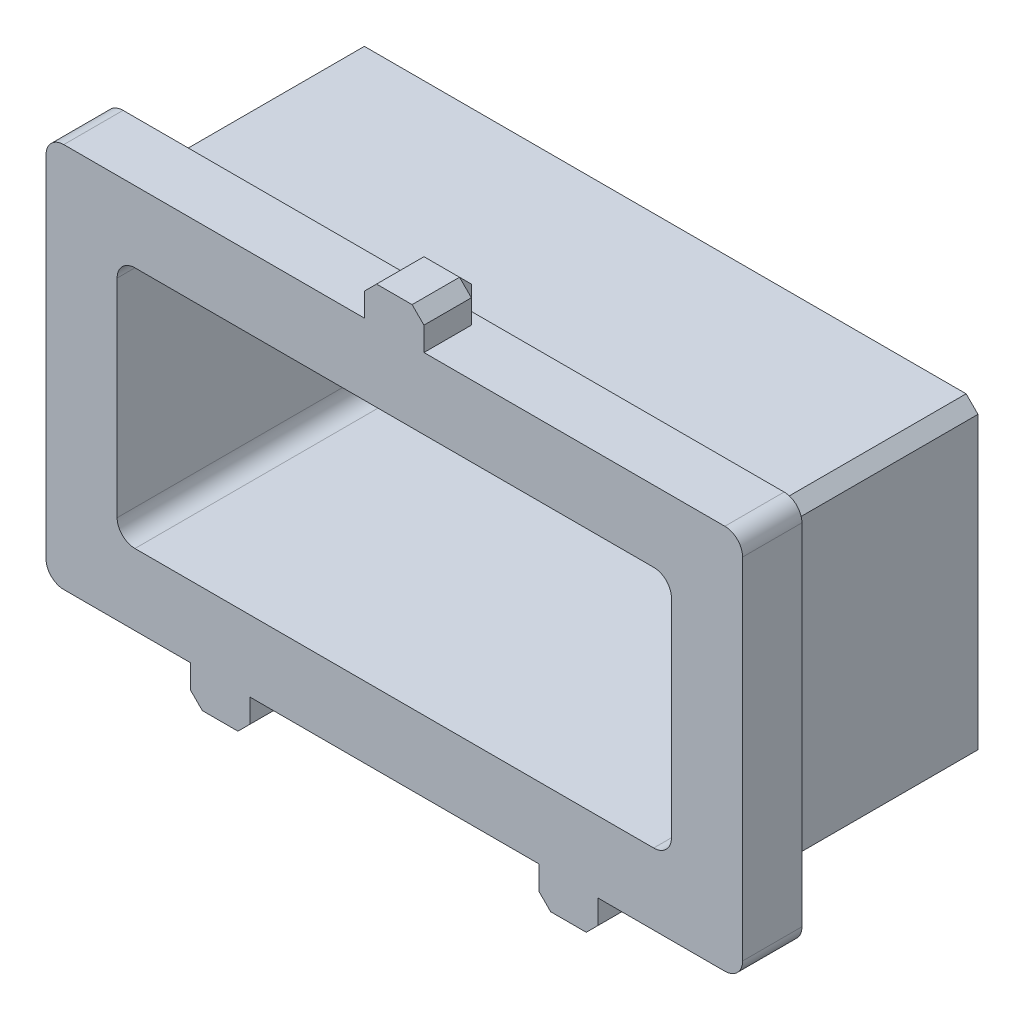
SolidWorks part; units mm, degrees
ref_plane "Front Plane" through (0, 0, 0) normal (0, 0, 1) x (1, 0, 0)
ref_plane "Top Plane" through (0, 0, 0) normal (0, 1, 0) x (1, 0, 0)
ref_plane "Right Plane" through (0, 0, 0) normal (1, 0, 0) x (0, 0, -1)
sketch "Sketch1" plane through (0, 0, 0) normal (0, 0, 1) x (1, 0, 0)
  line L4 (29.8204, 195.8186) -> (29.8204, 202.5496)
  line L5 (29.8204, 202.5496) -> (16.4219, 202.5496)
  line L6 (16.4219, 202.5496) -> (16.4219, 195.8186)
  line L7 (16.4219, 195.8186) -> (29.8204, 195.8186)
  line L8 (29.8204, 195.8186) -> (29.8204, 202.5496)
  line L9 (29.8204, 202.5496) -> (16.4219, 202.5496)
  line L10 (16.4219, 202.5496) -> (16.4219, 195.8186)
  line L11 (16.4219, 195.8186) -> (29.8204, 195.8186)
  dimension "D1" = 0
extrude "Extrude-Thin1" add sketch "Sketch1" along normal blind 5.8039 thin thin type one direction reverse wall 0.762
sketch "Sketch2" plane through (0, 0, 5.8039) normal (0, 0, 1) x (1, 0, 0)
  line L4 (16.4219, 195.8186) -> (29.8204, 195.8186)
  line L5 (29.8204, 195.8186) -> (29.8204, 202.5496)
  line L6 (29.8204, 202.5496) -> (16.4219, 202.5496)
  line L7 (16.4219, 202.5496) -> (16.4219, 195.8186)
  line L8 (16.4219, 195.8186) -> (29.8204, 195.8186)
  line L9 (29.8204, 195.8186) -> (29.8204, 202.5496)
  line L10 (29.8204, 202.5496) -> (16.4219, 202.5496)
  line L11 (16.4219, 202.5496) -> (16.4219, 195.8186)
  dimension "D1" = 0
extrude "Extrude-Thin2" add sketch "Sketch2" against normal blind 1.27 thin thin type one direction wall 0.762
sketch "Sketch4" plane through (0, 0, 5.8039) normal (0, 0, 1) x (1, 0, 0)
  line L0 (15.6599, 203.3116) -> (23.1211, 203.3116) construction
  line L1 (30.5824, 203.3116) -> (15.6599, 203.3116) construction
  line L2 (23.1211, 203.3116) -> (30.5824, 203.3116) construction
  line L3 (23.1211, 203.3116) -> (23.1211, 204.0736) construction
  line L4 (23.1211, 203.3116) -> (23.1211, 204.0736) construction
  line L5 (15.6599, 195.0566) -> (30.5824, 195.0566) construction
  line L6 (23.7561, 203.3116) -> (23.7561, 204.0736)
  line L7 (15.6599, 195.0566) -> (19.3905, 195.0566) construction
  line L8 (22.4861, 203.3116) -> (22.4861, 204.0736)
  line L9 (19.3905, 195.0566) -> (23.1211, 195.0566) construction
  line L10 (23.1211, 195.0566) -> (26.8517, 195.0566) construction
  line L11 (23.7561, 203.3116) -> (22.4861, 203.3116)
  line L12 (23.7561, 204.0736) -> (22.4861, 204.0736)
  line L13 (26.8517, 195.0566) -> (30.5824, 195.0566) construction
  line L14 (30.5824, 195.0566) -> (30.5824, 203.3116) construction
  line L16 (27.4867, 195.0566) -> (27.4867, 194.2946)
  line L17 (27.4867, 194.2946) -> (26.2167, 194.2946)
  line L18 (26.2167, 195.0566) -> (26.2167, 194.2946)
  line L19 (27.4867, 195.0566) -> (26.2167, 195.0566)
  line L20 (20.0255, 195.0566) -> (18.7555, 195.0566)
  line L21 (20.0255, 195.0566) -> (20.0255, 194.2946)
  line L22 (20.0255, 194.2946) -> (18.7555, 194.2946)
  line L23 (18.7555, 195.0566) -> (18.7555, 194.2946)
  point P11 (23.1211, 204.0736)
  dimension "D1" = 0.762
  dimension "D2" = 1.27
  dimension "D3" = 0.762
  dimension "D4" = 1.27
  dimension "D5" = 1.27
extrude "Boss-Extrude1" add sketch "Sketch4" against normal blind 1.27
chamfer "Chamfer1" distance 0.254 angle 45 19 edges at (29.8204, 195.8186, 2.2669) (16.4219, 195.8186, 2.2669) (29.8204, 202.5496, 2.2669) (16.4219, 202.5496, 2.2669) (27.4867, 194.2946, 5.1689) (26.2167, 194.2946, 5.1689) (20.0255, 194.2946, 5.1689) (18.7555, 194.2946, 5.1689) (23.7561, 204.0736, 5.1689) (22.4861, 204.0736, 5.1689) (26.8517, 194.2946, 4.5339) (18.7555, 194.6756, 4.5339) (19.3905, 194.2946, 4.5339) (20.0255, 194.6756, 4.5339) (23.1211, 204.0736, 4.5339)
fillet "Fillet1" radius 0.381 8 edges at (15.6599, 203.3116, 5.1689) (15.6599, 195.0566, 5.1689) (30.5824, 195.0566, 5.1689) (30.5824, 203.3116, 5.1689) (29.0584, 201.7876, 2.9019) (17.1839, 201.7876, 2.9019) (29.0584, 196.5806, 2.9019) (17.1839, 196.5806, 2.9019)
equation "\"D3@Sketch4\"=\"D1@Sketch4\""
equation "\"D4@Sketch4\"=\"D2@Sketch4\""
equation "\"D5@Sketch4\"=\"D2@Sketch4\""
